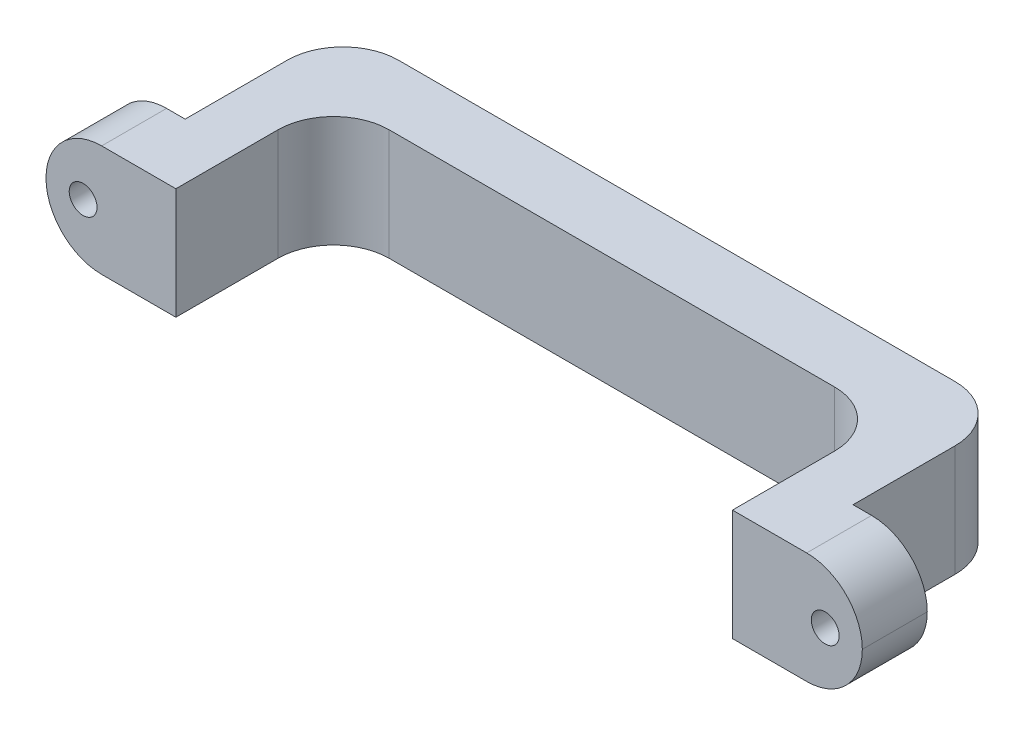
SolidWorks part; units mm, degrees
ref_plane "前视基准面" through (0, 0, 0) normal (0, 0, 1) x (1, 0, 0)
ref_plane "上视基准面" through (0, 0, 0) normal (0, 1, 0) x (1, 0, 0)
ref_plane "右视基准面" through (0, 0, 0) normal (1, 0, 0) x (0, 0, -1)
other "Configuration Table"
sketch "草图3" plane through (0, 0, 0) normal (0, 1, 0) x (1, 0, 0)
  line L0 (0, 0) -> (14, 0)
  line L1 (14, 0) -> (14, 17)
  line L5 (8, 24) -> (8, 7)
  line L6 (8, 7) -> (0, 7)
  line L7 (0, 7) -> (0, 0)
  line L13 (8, 24) -> (80, 24)
  line L14 (44, 24) -> (44, 17) construction
  line L15 (74, 17) -> (14, 17)
  line L16 (88, 7) -> (88, 0)
  line L17 (80, 7) -> (88, 7)
  line L18 (80, 24) -> (80, 7)
  line L19 (74, 0) -> (74, 17)
  line L20 (88, 0) -> (74, 0)
  point P12 (44, 17)
  point P13 (44, 24)
extrude "凸台-拉伸2" add sketch "草图3" along normal blind 12 contours L1 L15 L19 L20 L16 L17 L18 L13 L5 L6 L7 L0
sketch "草图6" plane through (0, 0, -7) normal (0, 0, -1) x (-1, 0, 0)
  circle A0 centre (-4, 6) radius 1.5
  circle A1 centre (-84, 6) radius 1.5
extrude "切除-拉伸2" cut sketch "草图6" against normal blind 12
fillet "圆角2" radius 6 8 edges at (14, 6, -17) (8, 6, -24) (80, 6, -24) (74, 6, -17) (0, 12, -3.5) (0, 0, -3.5) (88, 12, -3.5) (88, 0, -3.5)
